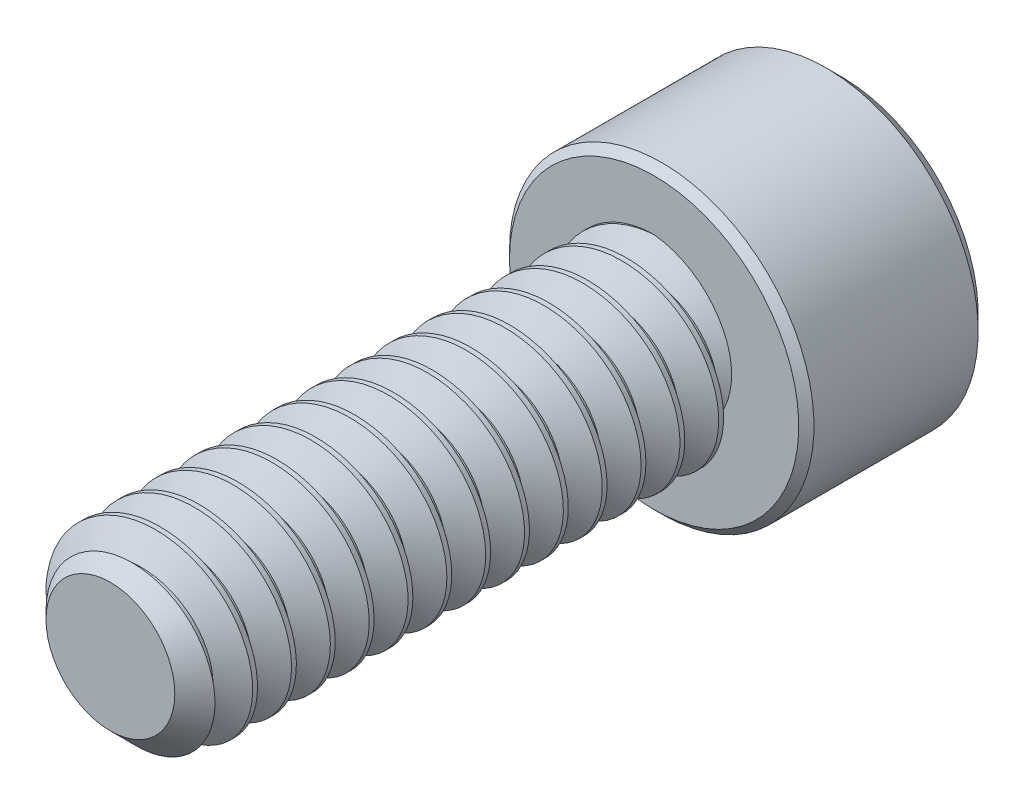
SolidWorks part; units mm, degrees
ref_plane "Front Plane" through (0, 0, 0) normal (0, 0, 1) x (1, 0, 0)
ref_plane "Top Plane" through (0, 0, 0) normal (0, 1, 0) x (1, 0, 0)
ref_plane "Right Plane" through (0, 0, 0) normal (1, 0, 0) x (0, 0, -1)
sketch "Sketch0" plane through (0, 0, 0) normal (1, 0, 0) x (0, 0, -1)
  line L0 (0, 0) -> (6.35, 0) construction
  point P2 (8.5344, 0)
  point P4 (0, 0)
  dimension "D1" = 6.35
  dimension "D2" = 2.1844
  dimension "Min Thread" = 0
sketch "Sketch1" plane through (0, 0, 0) normal (0, 0, 1) x (1, 0, 0)
  circle A0 centre (0, 0) radius 1.0922
  dimension "OD" = 2.1844
extrude "Extrude1" add sketch "Sketch1" against normal blind 6.35
sketch "Sketch2" plane through (0, 0, 0) normal (0, 0, 1) x (1, 0, 0)
  circle A0 centre (0, 0) radius 1.0922 construction
  circle A1 centre (0, 0) radius 1.0922
curve "Helix/Spiral1" pitch 0.4536 height 6.8036 radius 1.0922 centre (0, 0, 0) axis (0, 0, -1) start towards (0, 1, 0) parameters "pitch"=0.4536
chamfer "Chamfer3" distance 0.3402 angle 45 1 edges at (1.0922, 0, 0)
sketch "Sketch3" plane through (0, 0, 0) normal (1, 0, 0) x (0, 0, -1)
  line L0 (-0.3969, 1.0922) -> (-0.2268, 0.7976)
  line L1 (-0.2268, 0.7976) -> (-0.1701, 0.7976)
  line L2 (-0.1701, 0.7976) -> (0, 1.0922)
  line L3 (-0.3969, 1.0922) -> (0, 1.0922)
  line L4 (-0.1984, 1.0922) -> (-0.1984, 0.7976) construction
  line L5 (-0.3118, 0.9449) -> (-0.085, 0.9449) construction
  line L6 (0, 1.0922) -> (0, -1.0922) construction
  dimension "D1" = 0.0567
  dimension "D2" = 0.2268
  dimension "D3" = 60
sweep "Cut-Sweep1" cut profiles "Sketch3" path "Helix/Spiral1" align with end faces yes
sketch "Sketch5" plane through (0, 0, 0) normal (1, 0, 0) x (0, 0, -1)
  line L0 (6.35, -0.8061) -> (6.35, 0.7793) construction
  line L1 (6.35, 1.0922) -> (0, 1.0922)
  line L2 (6.35, 1.0922) -> (6.35, 0)
  line L3 (6.35, 0) -> (-0.3975, 0)
  line L4 (0, 0) -> (6.35, 0) construction
  line L5 (0, 1.0922) -> (-0.3975, 0)
  line L6 (0, 0) -> (8.89, 0) construction
  dimension "D1" = 70
  dimension "D3" = 2.54
revolve "partially thread" [suppressed] add sketch "Sketch5" angle 360 about L6
sketch "Sketch6" plane through (0, 0, -6.35) normal (0, 0, -1) x (-1, 0, 0)
  circle A0 centre (0, 0) radius 1.778
  dimension "head dia" = 3.556
extrude "Extrude2" add sketch "Sketch6" along normal blind 2.1844
sketch "Sketch7" plane through (0, 0, -8.5344) normal (0, 0, -1) x (-1, 0, 0)
  line L1 (0, 1.1457) -> (-0.9922, 0.5728)
  line L2 (-0.9922, 0.5728) -> (-0.9922, -0.5728)
  line L3 (-0.9922, -0.5728) -> (0, -1.1457)
  line L4 (0, -1.1457) -> (0.9922, -0.5728)
  line L5 (0.9922, -0.5728) -> (0.9922, 0.5728)
  line L6 (0.9922, 0.5728) -> (0, 1.1457)
  circle A0 centre (0, 0) radius 0.9922 construction
  dimension "hex dia" = 1.9844
extrude "Cut-Extrude1" cut sketch "Sketch7" against normal blind 1.4883
sketch "Sketch8" plane through (0, 0, -8.5344) normal (0, 0, -1) x (-1, 0, 0)
  circle A0 centre (0, 0) radius 1.1457
extrude "Cut-Extrude2" cut sketch "Sketch8" against normal through all draft 45
chamfer "Chamfer1" distance 0.1778 angle 45 1 edges at (-1.778, 0, -8.5344)
chamfer "Chamfer2" distance 0.0889 angle 45 1 edges at (-1.778, 0, -6.35)
sketch "Sketch9" plane through (0, 0, 0) normal (1, 0, 0) x (0, 0, -1)
  line L0 (0, 1.0922) -> (0, -1.0922) construction
  line L1 (1.5875, 1.0922) -> (1.5875, -1.0922) construction
  line L2 (8.5344, 1.778) -> (8.5344, -1.778) construction
  line L3 (6.35, 1.778) -> (6.35, -1.778) construction
  line L4 (6.35, 1.6891) -> (6.35, -1.6891) construction
  line L5 (8.5344, -1.6002) -> (8.5344, 1.6002) construction
  line L6 (6.35, -1.778) -> (6.35, 1.778) construction
  line L7 (0, 0.752) -> (0, -0.752) construction
  line L8 (-0.3969, 1.0922) -> (0, 1.0922) construction
  line L9 (1.5875, 0) -> (0, 0) construction
  dimension "D1" = 1.5875
equation "\"D3@Helix/Spiral1\" = \"screw length@Extrude1\"+\"pitch@Helix/Spiral1\""
equation "\"D1@Sketch3\" = \"pitch@Helix/Spiral1\"*.125"
equation "\"D2@Sketch3\" = \"pitch@Helix/Spiral1\"*.5"
equation "\"D1@Cut-Extrude1\" = \"hex dia@Sketch7\"*.75"
equation "\"D1@Chamfer1\" = \"head dia@Sketch6\"*.05"
equation "\"D1@Sketch9\" = \"pitch@Helix/Spiral1\"*3.50"
equation "\"D1@Chamfer2\" = \"D1@Chamfer1\"/2"
equation "\"D1@Chamfer3\" = \"pitch@Helix/Spiral1\"*.750"
equation "\"D1@Sketch0\" = \"screw length@Extrude1\""
equation "\"D2@Sketch0\" = \"head depth@Extrude2\""
